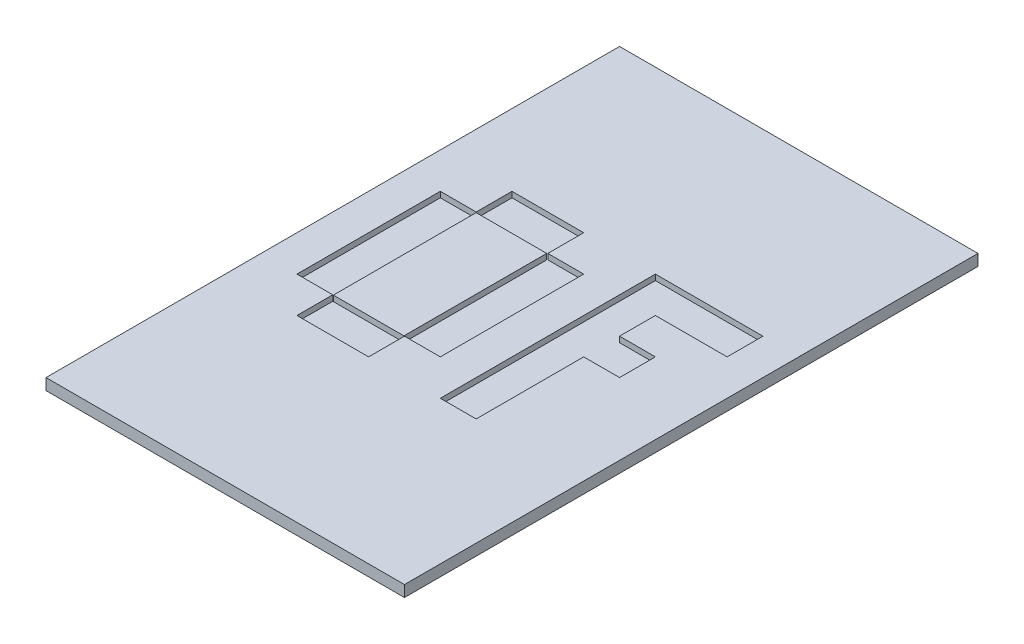
SolidWorks part; units mm, degrees
ref_plane "Front Plane" through (0, 0, 0) normal (0, 0, 1) x (1, 0, 0)
ref_plane "Top Plane" through (0, 0, 0) normal (0, 1, 0) x (1, 0, 0)
ref_plane "Right Plane" through (0, 0, 0) normal (1, 0, 0) x (0, 0, -1)
sketch "Sketch1" plane through (0, 0, 0) normal (0, 1, 0) x (1, 0, 0)
  line L1 (0, 0) -> (127, 0)
  line L2 (0, 0) -> (0, 203.2)
  line L3 (0, 203.2) -> (127, 203.2)
  line L4 (127, 0) -> (127, 203.2)
  dimension "D1" = 127
  dimension "D2" = 203.2
extrude "Boss-Extrude1" add sketch "Sketch1" along normal blind 4 contours L1 L4 L3 L2
sketch "Sketch2" plane through (0, 4, 0) normal (0, 1, 0) x (1, 0, 0)
  line L0 (0, 0) -> (0, 203.2) construction
  line L1 (12.7, 127) -> (25.4, 127)
  line L2 (12.7, 127) -> (12.7, 76.2)
  line L3 (12.7, 76.2) -> (25.4, 76.2)
  line L4 (25.4, 127) -> (25.4, 76.2)
  line L5 (0, 0) -> (127, 0) construction
  line L6 (88.9, 127) -> (88.9, 114.3)
  line L7 (25.4, 127) -> (50.8, 127)
  line L8 (25.4, 127) -> (25.4, 139.7)
  line L9 (25.4, 139.7) -> (50.8, 139.7)
  line L10 (50.8, 127) -> (50.8, 139.7)
  line L11 (25.4, 76.2) -> (50.8, 76.2)
  line L12 (25.4, 76.2) -> (25.4, 63.5)
  line L13 (25.4, 63.5) -> (50.8, 63.5)
  line L14 (50.8, 76.2) -> (50.8, 63.5)
  line L15 (50.8, 127) -> (63.5, 127)
  line L16 (50.8, 127) -> (50.8, 76.2)
  line L17 (50.8, 76.2) -> (63.5, 76.2)
  line L18 (63.5, 127) -> (63.5, 76.2)
  line L19 (76.2, 63.5) -> (88.9, 63.5)
  line L20 (76.2, 63.5) -> (76.2, 139.7)
  line L21 (76.2, 139.7) -> (88.9, 139.7)
  line L23 (88.9, 139.7) -> (114.3, 139.7)
  line L25 (88.9, 127) -> (114.3, 127)
  line L26 (114.3, 139.7) -> (114.3, 127)
  line L27 (88.9, 114.3) -> (101.6, 114.3)
  line L29 (88.9, 101.6) -> (101.6, 101.6)
  line L30 (101.6, 114.3) -> (101.6, 101.6)
  line L31 (88.9, 101.6) -> (88.9, 63.5)
  point P27 (95.25, 114.3)
  dimension "D1" = 12.7
  dimension "D2" = 50.8
  dimension "D3" = 76.2
  dimension "D4" = 12.7
  dimension "D5" = 25.4
  dimension "D6" = 12.7
  dimension "D7" = 12.7
  dimension "D8" = 12.7
  dimension "D9" = 76.2
  dimension "D10" = 12.7
  dimension "D11" = 12.7
  dimension "D12" = 25.4
  dimension "D13" = 12.7
  dimension "D14" = 12.7
  dimension "D15" = 12.7
extrude "Cut-Extrude4" cut sketch "Sketch2" against normal blind 2 contours L31 L19 L20 L21 L23 L26 L25 L6 L27 L30 L29
extrude "Cut-Extrude8" cut sketch "Sketch2<5>" against normal blind 2 contours L4 L1 L2 L3 | L18 L15 L16 L17 | L7 L10 L9 L8 | L14 L11 L12 L13 | L16 L7 L4 L11 region at (19.05, 4, -101.6) region at (38.1, 4, -101.6) region at (38.1, 4, -133.35) region at (38.1, 4, -69.85) region at (57.15, 4, -101.6)
sketch "Sketch2<5>" plane through (0, 4, 0) normal (0, 1, 0) x (1, 0, 0) same geometry as "Sketch2"
sketch "Sketch4" plane through (0, 2, 0) normal (0, 1, 0) x (1, 0, 0)
  line L0 (0, 0) -> (127, 0) construction
  line L1 (25.6, 126.8) -> (50.6, 126.8)
  line L2 (25.6, 126.8) -> (25.6, 76.2)
  line L3 (25.6, 76.2) -> (50.6, 76.2)
  line L4 (50.6, 126.8) -> (50.6, 76.2)
  line L5 (63.5, 127) -> (63.5, 76.2) construction
  line L7 (12.7, 127) -> (12.7, 76.2) construction
  line L8 (25.4, 139.7) -> (50.8, 139.7) construction
  dimension "D1" = 12.9
  dimension "D2" = 12.9
  dimension "D3" = 76.2
  dimension "D4" = 12.9
extrude "Boss-Extrude10" add sketch "Sketch4" along normal blind 2 separate body
